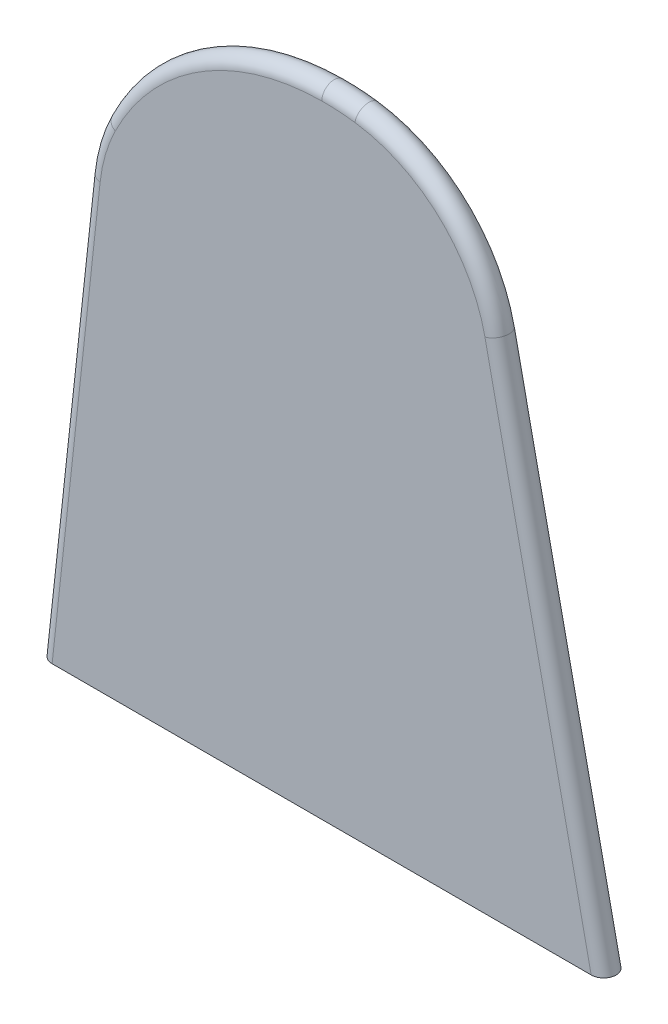
SolidWorks part; units mm, degrees
material "Polyurethane Foam Rigid"
ref_plane "Front Plane" through (0, 0, 0) normal (0, 0, 1) x (1, 0, 0)
ref_plane "Top Plane" through (0, 0, 0) normal (0, 1, 0) x (1, 0, 0)
ref_plane "Right Plane" through (0, 0, 0) normal (1, 0, 0) x (0, 0, -1)
sketch "Sketch1" plane through (0, 0, 0) normal (0, 0, 1) x (1, 0, 0)
  line L0 (0, 0) -> (0, 57.15)
  line L1 (0, 0) -> (25.4, 0)
  line L2 (0, 0) -> (-25.4, 0)
  line L3 (25.4, 0) -> (14.3691, 51.8394)
  line L4 (-25.4, 0) -> (-20.8548, 41.7533)
  arc A0 (-20.8548, 41.7533) -> (0, 57.15) centre (0.1719, 35.0949) cw
  arc A1 (0, 57.15) -> (14.3691, 51.8394) centre (0.2317, 35.6822) cw
  dimension "D1" = 57.15
  dimension "D2" = 25.4
  dimension "D3" = 25.4
extrude "Boss-Extrude1" add sketch "Sketch1" along normal blind 2.21 contours A1 L0 L1 L3 | A0 L4 L2 L0 region at (-10.9689, 25.6575, 0) region at (9.9691, 25.0051, 0)
fillet "Fillet3" radius 15 1 edges at (-20.8548, 41.7533, 1.105)
fillet "Fillet4" radius 15 1 edges at (14.3691, 51.8394, 1.105)
fillet "Fillet5" 12 edges at (1.5727, 57.1093, 0) (-11.5291, 53.791, 0) (-23.2309, 19.9258, 0) (20.5895, 22.6068, 0) (11.3152, 53.0827, 0) (-20.5477, 42.4356, 0) (1.5727, 57.1093, 2.21) (-11.5291, 53.791, 2.21) (-23.2309, 19.9258, 2.21) (20.5895, 22.6068, 2.21) (11.3152, 53.0827, 2.21) (-20.5477, 42.4356, 2.21) type full round first side face at (-3.1186, 35.5645, 0) second side face at (-3.1186, 35.5645, 2.21) middle face at (-23.2309, 19.9258, 1.105) middle face at (-20.4367, 42.4032, 1.105) middle face at (-10.6619, 52.4055, 1.105) middle face at (1.5709, 57.0806, 1.105) middle face at (10.3869, 52.0832, 1.105) middle face at (20.5895, 22.6068, 1.105)
